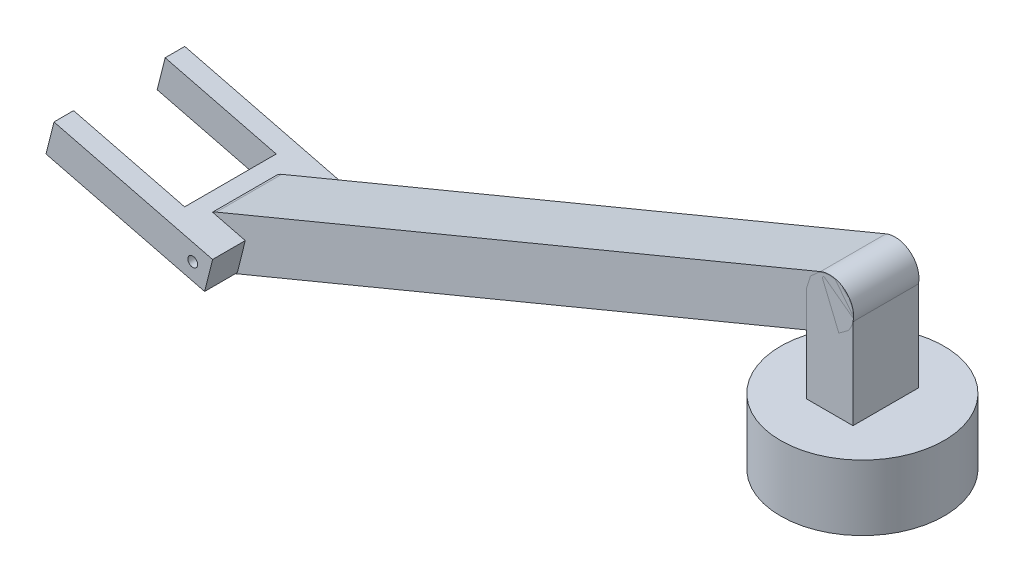
SolidWorks part; units mm, degrees
ref_plane "前基準面" through (0, 0, 0) normal (0, 0, 1) x (1, 0, 0)
ref_plane "上基準面" through (0, 0, 0) normal (0, 1, 0) x (1, 0, 0)
ref_plane "右基準面" through (0, 0, 0) normal (1, 0, 0) x (0, 0, -1)
sketch "草圖2" plane through (0, 0, 0) normal (0, 1, 0) x (1, 0, 0)
  circle A0 centre (0, 0) radius 25
  dimension "D1" = 50
extrude "填料-伸長1" add sketch "草圖2" along normal blind 20
sketch "草圖4" plane through (0, 0, 0) normal (0, 0, 1) x (1, 0, 0)
  line L0 (0, 20) -> (0, 49.1014) construction
  line L1 (-7.1256, 20) -> (-7.1256, 49.1014)
  line L2 (7.1256, 20) -> (7.1256, 49.1014)
  line L3 (25, 20) -> (-25, 20) construction
  arc A0 (-7.1256, 20) -> (7.1256, 20) centre (0, 20) ccw
  arc A1 (7.1256, 49.1014) -> (-7.1256, 49.1014) centre (0, 49.1014) ccw
  point P2 (0, 34.5507)
extrude "填料-伸長2" add sketch "草圖4" along normal mid plane 20
sketch "草圖5" plane through (0, 0, 0) normal (0, 0, 1) x (1, 0, 0)
  line L0 (0, 49.1014) -> (-184.7435, -27.5135) construction
  line L1 (2.7972, 42.3564) -> (-181.9463, -34.2584)
  line L2 (-2.7972, 55.8463) -> (-187.5407, -20.7685)
  arc A0 (2.7972, 42.3564) -> (-2.7972, 55.8463) centre (0, 49.1014) ccw
  arc A1 (-187.5407, -20.7685) -> (-181.9463, -34.2584) centre (-184.7435, -27.5135) ccw
  point P3 (-92.3718, 10.7939)
  dimension "D1" = 200
extrude "填料-伸長3" add sketch "草圖5" along normal mid plane 20 separate body
sketch "草圖6" plane through (0, 0, 0) normal (0, 0, 1) x (1, 0, 0)
  line L0 (-181.1096, -33.5794) -> (-178.6776, -23.8796)
  line L1 (-181.1096, -33.5794) -> (-229.6084, -21.4194)
  line L2 (-178.6776, -23.8796) -> (-227.1764, -11.7196)
  line L3 (-229.6084, -21.4194) -> (-227.1764, -11.7196)
  line L4 (-184.7435, -27.5135) -> (-179.8936, -28.7295) construction
  circle A0 centre (-184.7435, -27.5135) radius 1.5
  arc A1 (-187.5407, -20.7685) -> (-181.9463, -34.2584) centre (-184.7435, -27.5135) ccw construction
  point P10 (-229.6084, -21.4194)
  dimension "D4" = 3
  dimension "D1" = 50
  dimension "D2" = 10
  dimension "D3" = 5
extrude "填料-伸長4" add sketch "草圖6" along normal mid plane 60
sketch "草圖7" plane through (-16.2013, -64.617, 0) normal (0.2432, 0.97, 0) x (0.97, -0.2432, 0)
  line L0 (-217.5055, -30) -> (-217.5055, 30) construction
  line L1 (-217.5055, 14) -> (-182.5055, 14)
  line L2 (-217.5055, 14) -> (-217.5055, -14)
  line L3 (-217.5055, -14) -> (-182.5055, -14)
  line L4 (-182.5055, 14) -> (-182.5055, -14)
  line L5 (-167.5055, 30) -> (-217.5055, 30) construction
  line L6 (-167.5055, -30) -> (-217.5055, -30) construction
  line L7 (-167.5055, 10) -> (-167.5055, 30) construction
  line L9 (-217.5055, 30) -> (-134.5505, 30)
  line L10 (-217.5055, 30) -> (-217.5055, 20)
  line L11 (-217.5055, 20) -> (-134.5505, 20)
  line L12 (-134.5505, 30) -> (-134.5505, 20)
  line L13 (-217.5055, -30) -> (-134.5505, -30)
  line L14 (-217.5055, -30) -> (-217.5055, -20)
  line L15 (-217.5055, -20) -> (-134.5505, -20)
  line L16 (-134.5505, -30) -> (-134.5505, -20)
  dimension "D1" = 16
  dimension "D2" = 16
  dimension "D3" = 15
  dimension "D4" = 10
  dimension "D5" = 10
extrude "除料-伸長1" cut sketch "草圖7" against normal through all
